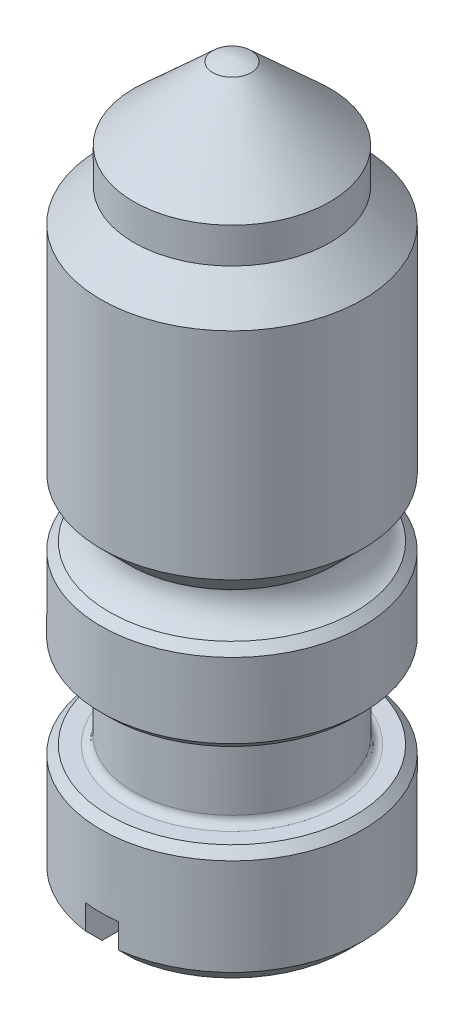
SolidWorks part; units mm, degrees
material "1.0037 (S235JR)"
ref_plane "Front Plane" through (0, 0, 0) normal (0, 0, 1) x (1, 0, 0)
ref_plane "Top Plane" through (0, 0, 0) normal (0, 1, 0) x (1, 0, 0)
ref_plane "Right Plane" through (0, 0, 0) normal (1, 0, 0) x (0, 0, -1)
sketch "Sketch1" plane through (0, 0, 0) normal (0, 0, 1) x (1, 0, 0)
  line L0 (0, 0) -> (-3.9972, 0)
  line L2 (-3.9965, 6.2908) -> (-3, 6.2908)
  line L3 (-3, 6.2908) -> (-3, 3.6957)
  line L6 (-3, 3.6957) -> (-3.9972, 3.6957)
  line L9 (-3.9971, 10.8671) -> (-3.9971, 17.4465)
  line L10 (-3.9971, 17.4465) -> (-2.9935, 18.45)
  line L13 (0, 21.8841) -> (0, 0)
  line L14 (-3.9971, 10.8671) -> (-3.13, 10)
  line L20 (-3.9965, 9.0696) -> (-3.13, 9.0696)
  line L23 (-3.13, 9.0696) -> (-3.13, 10)
  line L24 (-3, 18.45) -> (1.0892, 18.45) construction
  line L27 (-3.9965, 9.0696) -> (-3.9965, 6.2908)
  line L28 (-3.9972, 3.6957) -> (-3.9972, 0)
  line L30 (-9, 10) -> (0.1296, 10) construction
  line L31 (-2.9935, 18.45) -> (-2.9935, 19.5285)
  line L32 (-2.9935, 19.5285) -> (-0.5842, 21.7346)
  line L33 (-3.13, 10) -> (-3.13, 18.3135) construction
  arc A1 (-0.5842, 21.7346) -> (0, 21.8841) centre (0.2128, 19.836) cw
  dimension "D1" = 3.9972
  dimension "D13" = 2.0591
  dimension "D2" = 3.9965
  dimension "D3" = 2.7788
  dimension "D4" = 2.5951
  dimension "D5" = 3
  dimension "D6" = 3.13
  dimension "D7" = 45
  dimension "D8" = 45
  dimension "D9" = 3.9971
  dimension "D10" = 9.0696
  dimension "D11" = 47.521
  dimension "D12" = 4.4376
  dimension "D14" = 1.0785
  dimension "D15" = 1.0035
revolve "Revolve1" add sketch "Sketch1" angle 360 about L13
cosmetic thread "Rosca cosmética6" parameters "D1"=8.5, "D2"=6.619
cosmetic thread "Rosca cosmética7" parameters "D1"=8, "D2"=6.619
fillet "Redondeo1" radius 0.25 2 edges at (-3, 3.6957, 0) (-3, 6.2908, 0)
chamfer "Chaflán7" distance 0.25 angle 45 3 edges at (-3.9965, 9.0696, 0) (-3.9972, 3.6957, 0) (-3.9965, 6.2908, 0)
chamfer "Chaflán9" distance 0.5 angle 45 1 edges at (-3.9972, 0, 0)
ref_plane "Plano1" through (0, 0, 10) normal (0, 0, 1) x (1, 0, 0)
sketch "Croquis1" plane through (0, 0, 10) normal (0, 0, 1) x (1, 0, 0)
  line L0 (0, 0) -> (0, 1.25) construction
  line L1 (-3.4972, 0) -> (3.4972, 0) construction
  line L3 (-0.5, 1.25) -> (0.5, 1.25)
  line L4 (-0.5, 1.25) -> (-0.5, 0)
  line L5 (-0.5, 0) -> (0.5, 0)
  line L6 (0.5, 1.25) -> (0.5, 0)
  line L7 (-0.5, 1.25) -> (0.5, 0) construction
  line L8 (-0.5, 0) -> (0.5, 1.25) construction
  point P4 (0, 0.625)
  dimension "D1" = 1.25
  dimension "D2" = 1
extrude "Cortar-Extruir1" cut sketch "Croquis1" against normal blind 40
fillet "Redondeo2" radius 1 1 edges at (-3.13, 9.0696, 0)
